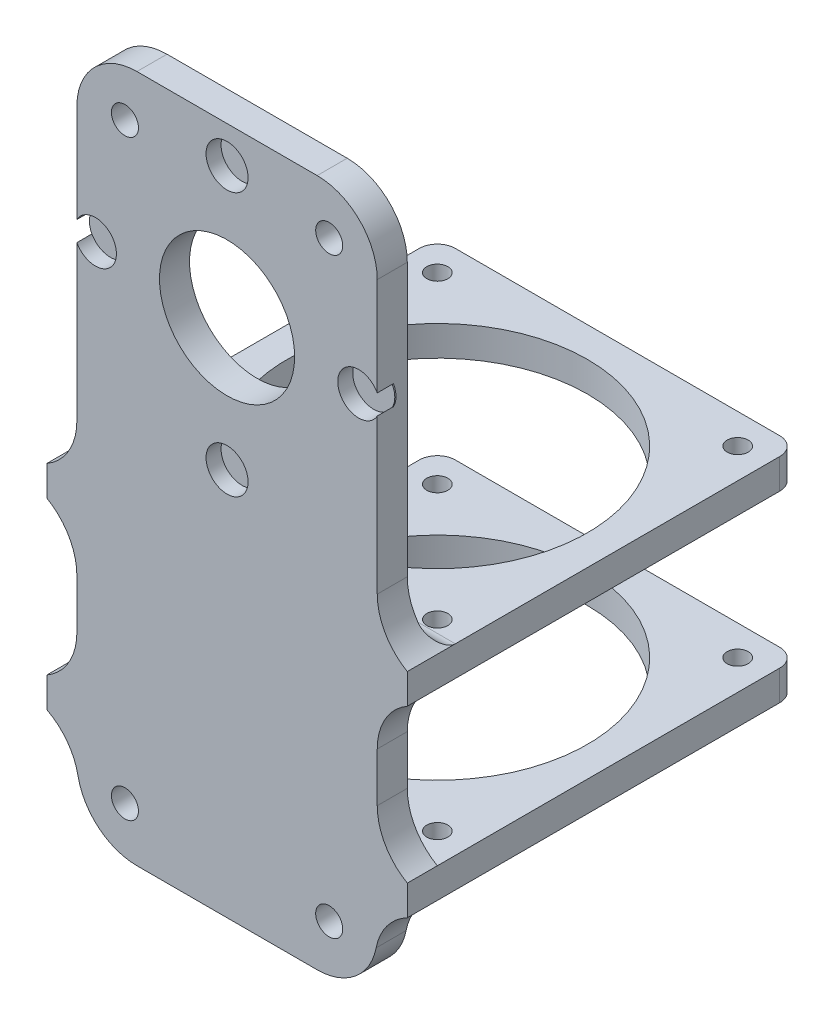
SolidWorks part; units mm, degrees
ref_plane "Front Plane" through (0, 0, 0) normal (0, 0, 1) x (1, 0, 0)
ref_plane "Top Plane" through (0, 0, 0) normal (0, 1, 0) x (1, 0, 0)
ref_plane "Right Plane" through (0, 0, 0) normal (1, 0, 0) x (0, 0, -1)
sketch "Sketch1" plane through (0, 0, 0) normal (0, 0, 1) x (1, 0, 0)
  line L0 (-21.9203, 0) -> (0, 21.9203) construction
  line L1 (0, 21.9203) -> (21.9203, 0) construction
  line L2 (21.9203, 0) -> (0, -21.9203) construction
  line L3 (0, -21.9203) -> (-21.9203, 0) construction
  line L5 (-15, -33) -> (15, -33)
  line L6 (-25, -23) -> (-25, 71.5)
  line L7 (-15, 81.5) -> (15, 81.5)
  line L8 (25, -23) -> (25, 71.5)
  circle A0 centre (0, 0) radius 11.25
  circle A1 centre (-21.9203, 0) radius 1.75
  circle A2 centre (0, 21.9203) radius 1.75
  circle A3 centre (21.9203, 0) radius 1.75
  circle A4 centre (0, -21.9203) radius 1.75
  circle A5 centre (0, 53.5) radius 11.25
  arc A6 (15, -33) -> (25, -23) centre (15, -23) ccw
  arc A7 (-15, -33) -> (-25, -23) centre (-15, -23) cw
  arc A8 (-25, 71.5) -> (-15, 81.5) centre (-15, 71.5) cw
  arc A9 (25, 71.5) -> (15, 81.5) centre (15, 71.5) ccw
  circle A10 centre (-17, 73.5) radius 2.25
  circle A11 centre (17, 73.5) radius 2.25
  circle A12 centre (-17, -25) radius 2.25
  circle A13 centre (17, -25) radius 2.25
  circle A14 centre (0, 75.4203) radius 1.75
  circle A15 centre (-21.9203, 53.5) radius 1.75
  circle A16 centre (21.9203, 53.5) radius 1.75
  circle A17 centre (0, 31.5797) radius 1.75
  point P11 (0, -33)
  point P18 (25, -33)
  point P28 (-25, 81.5)
  point P31 (25, 81.5)
  point P45 (0, 81.5)
  dimension "D6" = 22.5
  dimension "D2" = 3.5
  dimension "D8" = 22.5
  dimension "D11" = 10
  dimension "D13" = 4.5
  dimension "D1" = 31
  dimension "D3" = 90
  dimension "D4" = 31
  dimension "D5" = 31
  dimension "D7" = 53.5
  dimension "D9" = 50
  dimension "D10" = 114.5
  dimension "D12" = 33
  dimension "D14" = 8
  dimension "D15" = 8
  dimension "D16" = 8
  dimension "D17" = 8
  dimension "D18" = 98.5
  dimension "D19" = 34
  dimension "D23" = 31
  dimension "D24" = 31
  dimension "D25" = 31
extrude "Boss-Extrude1" add sketch "Sketch1" along normal blind 5 contours L6 A8 L7 A9 L8 A6 L5 A7 | A5 | A11 | A14 | A10 | A15 | A16 | A17 | A12 | A13
sketch "Sketch5" plane through (0, -33, 0) normal (0, -1, 0) x (1, 0, 0)
  line L0 (-15, 0.6) -> (15, 0.6) construction
  line L1 (-15, 0) -> (15, 0) construction
  text T0 "V2.1" font "Rubik" height in points 9
  dimension "D1" = 0.6
extrude "Cut-Extrude2" cut sketch "Sketch5" against normal blind 0.6
sketch "Sketch6" plane through (0, 0, 5) normal (0, 0, 1) x (1, 0, 0)
  line L0 (-15, 81.5) -> (15, 81.5) construction
  line L1 (-30, 12.5) -> (30, 12.5) construction
  line L2 (-30, 12.5) -> (-30, -13) construction
  line L3 (-30, -13) -> (30, -13) construction
  line L4 (30, 12.5) -> (30, -13) construction
  line L5 (-15, -33) -> (15, -33) construction
  line L6 (-30, 12.5) -> (30, 12.5)
  line L7 (-30, 12.5) -> (-30, 17.5)
  line L8 (-30, 17.5) -> (30, 17.5)
  line L9 (30, 12.5) -> (30, 17.5)
  line L10 (-30, -13) -> (30, -13)
  line L11 (-30, -13) -> (-30, -18)
  line L12 (-30, -18) -> (30, -18)
  line L13 (30, -13) -> (30, -18)
  point P6 (0, 81.5)
  point P7 (0, 12.5)
  dimension "D1" = 25.5
  dimension "D2" = 60
  dimension "D3" = 5
  dimension "D4" = 15
extrude "Boss-Extrude2" add sketch "Sketch6" against normal blind 65
sketch "Sketch7" plane through (0, 0, 5) normal (0, 0, 1) x (1, 0, 0)
  line L0 (30, -18) -> (30, -13) construction
  line L1 (30, 17.5) -> (-30, 17.5)
  line L2 (30, 17.5) -> (30, 12.5)
  line L3 (30, 12.5) -> (-30, 12.5)
  line L4 (-30, 17.5) -> (-30, 12.5)
  line L5 (30, -13) -> (-30, -13)
  line L6 (30, -13) -> (30, -18)
  line L7 (30, -18) -> (-30, -18)
  line L8 (-30, -13) -> (-30, -18)
extrude "Boss-Extrude3" add sketch "Sketch7" along normal up to surface (-5 mm away) up to face at (0, 57.5237, 0)
sketch "Sketch8" plane through (0, -18, 0) normal (0, -1, 0) x (1, 0, 0)
  line L0 (-30, -60) -> (30, -60) construction
  line L1 (-25, -5) -> (25, -5) construction
  line L2 (-25, -5) -> (-25, -55) construction
  line L3 (-25, -55) -> (25, -55) construction
  line L4 (25, -5) -> (25, -55) construction
  line L8 (-30, -60) -> (30, -60) construction
  circle A0 centre (-25, -5) radius 1.75
  circle A1 centre (25, -5) radius 1.75
  circle A2 centre (-25, -55) radius 1.75
  circle A3 centre (25, -55) radius 1.75
  circle A4 centre (0, -30) radius 25
  point P13 (0, -60)
  point P14 (0, -5)
  point P16 (25, -30)
  dimension "D1" = 3.5
  dimension "D2" = 50
  dimension "D3" = 50
  dimension "D4" = 30
extrude "Cut-Extrude3" cut sketch "Sketch8" against normal up to surface (35.5 mm away) up to face at (0, 17.5, -12.5)
fillet "Fillet1" radius 10 8 edges at (-25, 17.5, 2.5) (-25, -13, 2.5) (-25, 12.5, 2.5) (-25, -18, 2.5) (25, -18, 2.5) (25, 12.5, 2.5) (25, -13, 2.5) (25, 17.5, 2.5)
fillet "Fillet2" radius 3 6 edges at (-30, 15, -60) (-30, -15.5, -60) (30, 15, -60) (30, -15.5, -60) (0, 17.5, 0) (0, -18, 0)
sketch "Sketch9" plane through (0, 0, 5) normal (0, 0, 1) x (1, 0, 0)
  circle A0 centre (0, 75.4203) radius 3.5
  circle A1 centre (-21.9203, 53.5) radius 3.5
  circle A2 centre (0, 31.5797) radius 3.5
  circle A3 centre (21.9203, 53.5) radius 3.5
  dimension "D1" = 7
extrude "Cut-Extrude4" cut sketch "Sketch9" against normal blind 2.5
sketch "Sketch10" plane through (0, 0, 2.5) normal (0, 0, 1) x (1, 0, 0)
  circle A0 centre (0, 75.4203) radius 3.5
  circle A1 centre (21.9203, 53.5) radius 3.5
  circle A2 centre (0, 31.5797) radius 3.5
  circle A3 centre (-21.9203, 53.5) radius 3.5
  circle A4 centre (0, 75.4203) radius 3.5 construction
extrude "Boss-Extrude4" add sketch "Sketch10" against normal blind 0.2
